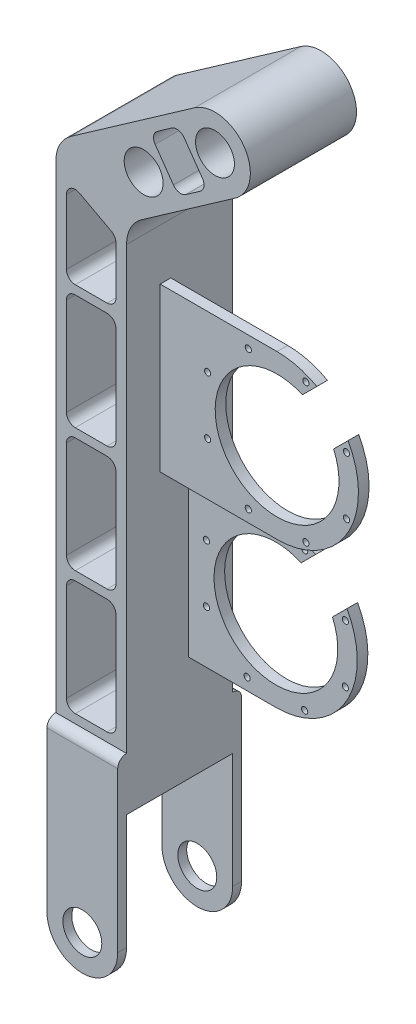
SolidWorks part; units mm, degrees
material "6061 合金"
ref_plane "前视基准面" through (0, 0, 0) normal (0, 0, 1) x (1, 0, 0)
ref_plane "上视基准面" through (0, 0, 0) normal (0, 1, 0) x (1, 0, 0)
ref_plane "右视基准面" through (0, 0, 0) normal (1, 0, 0) x (0, 0, -1)
other "Configuration Table"
sketch "草图1" plane through (0, 0, 0) normal (0, 0, 1) x (1, 0, 0)
  circle A0 centre (0, 0) radius 20
  circle A1 centre (0, 0) radius 11
  dimension "D1" = 40
  dimension "D2" = 22
extrude "凸台-拉伸1" add sketch "草图1" along normal blind 60 contours A1 | A0
ref_plane "基准面1" through (0, 0, 30) normal (0, 0, 1) x (1, 0, 0)
sketch "草图2" plane through (0, 0, 30) normal (0, 0, 1) x (1, 0, 0)
  line L0 (0, 0) -> (-70, -49.0145) construction
  line L1 (-70, -49.0145) -> (-70, -349.0145) construction
  line L2 (0, -57.3148) -> (0, 49.9409) construction
  line L3 (-56.8582, 0) -> (46.4003, 0) construction
  line L4 (-11.4715, 16.383) -> (-90, -38.6032)
  line L5 (11.4715, -16.383) -> (-50, -59.4259)
  line L6 (-90, -38.6032) -> (-90, -349.0145)
  line L7 (-50, -59.4259) -> (-50, -349.0145)
  line L8 (-90, -349.0145) -> (-50, -349.0145)
  circle A2 centre (0, 0) radius 20 construction
  arc A3 (-11.4715, 16.383) -> (11.4715, -16.383) centre (0, 0) ccw
  dimension "D1" = 55
  dimension "D2" = 300
  dimension "D3" = 70
  dimension "D4" = 40
  dimension "D5" = 40
extrude "凸台-拉伸2" add sketch "草图2" along normal mid plane 60 contours L7 L8 L6 L4 A3 L5
sketch "草图4" plane through (0, 0, 60) normal (0, 0, 1) x (1, 0, 0)
  line L0 (-90, -38.6032) -> (-90, -349.0145) construction
  line L1 (-90, -319.0145) -> (-50, -319.0145)
  line L2 (-90, -319.0145) -> (-90, -414.1256)
  line L4 (-50, -319.0145) -> (-50, -414.1256)
  line L5 (-50, -59.4259) -> (-50, -349.0145) construction
  line L6 (-90, -349.0145) -> (-50, -349.0145) construction
  line L7 (0, 0) -> (-70, -414.1256) construction
  arc A0 (-90, -414.1256) -> (-50, -414.1256) centre (-70, -414.1256) ccw
  circle A1 centre (-70, -414.1256) radius 11
  dimension "D3" = 22
  dimension "D1" = 30
  dimension "D2" = 420
extrude "凸台-拉伸3" add sketch "草图4" along normal blind 5
sketch "草图8" plane through (0, 0, 60) normal (0, 0, 1) x (1, 0, 0)
  line L1 (0, 0) -> (-70, -414.1256) construction
  line L2 (0, 0) -> (-40.3295, -29.5556) construction
  line L3 (-40.3295, -29.5556) -> (-70, -414.1256) construction
  circle A0 centre (-40.3295, -29.5556) radius 11
  dimension "D1" = 22
  dimension "D2" = 50
  dimension "D3" = 44.17
extrude "切除-拉伸1" cut sketch "草图8" against normal blind 100
mirror "镜向1" about plane through (0, 0, 30) normal (0, 0, 1) of "凸台-拉伸3"
sketch "草图5" plane through (0, 0, 0) normal (0, 1, 0) x (1, 0, 0)
  line L0 (0, 0) -> (0, -78.0582) construction
ref_plane "基准面2" through (-70, 0, 0) normal (-1, 0, 0) x (0, 0, 1)
sketch "草图7" plane through (-70, 0, 0) normal (-1, 0, 0) x (0, 0, 1)
  line L0 (-34.1239, -414.1256) -> (109.535, -414.1256) construction
fillet "圆角4" radius 20 2 edges at (-90, -38.6032, 30) (-50, -59.4259, 30)
fillet "圆角1" [suppressed] radius 50
fillet "圆角2" [suppressed] radius 3
sketch "草图9" plane through (0, 0, 65) normal (0, 0, 1) x (1, 0, 0)
  circle A0 centre (-70, -414.1256) radius 13
  dimension "D1" = 26
extrude "切除-拉伸2" [suppressed] cut sketch "草图9" against normal blind 0.75
sketch "草图10" plane through (0, 0, -5) normal (0, 0, -1) x (-1, 0, 0)
  circle A0 centre (70, -414.1256) radius 13
  dimension "D1" = 26
extrude "切除-拉伸3" [suppressed] cut sketch "草图10" against normal blind 0.75 contours A0
sketch "草图11" plane through (-90, 0, 0) normal (-1, 0, 0) x (0, 0, 1)
  circle A0 centre (48.5, -118.9949) radius 2.75
  circle A1 centre (48.5, -183.9949) radius 2.75
  circle A2 centre (48.5, -248.9949) radius 2.75
  circle A3 centre (11.5, -248.9949) radius 2.75
  circle A4 centre (11.5, -183.9949) radius 2.75
  circle A5 centre (11.5, -118.9949) radius 2.75
  dimension "D1" = 5.5
extrude "切除-拉伸4" [suppressed] cut sketch "草图11" against normal through all contours A1 | A2 | A0 | A3 | A4 | A5
sketch "草图12" [suppressed] plane through (-90, 0, 0) normal (-1, 0, 0) x (0, 0, 1)
  line L0 (30, -62.0134) -> (30, -339.6946) construction
  line L1 (10, -128.9949) -> (50, -128.9949)
  line L2 (10, -128.9949) -> (10, -173.9949)
  line L3 (10, -173.9949) -> (50, -173.9949)
  line L4 (50, -128.9949) -> (50, -173.9949)
  line L5 (10, -193.9949) -> (50, -193.9949)
  line L6 (10, -193.9949) -> (10, -238.9949)
  line L7 (10, -238.9949) -> (50, -238.9949)
  line L8 (50, -193.9949) -> (50, -238.9949)
  line L9 (10, -258.9949) -> (50, -258.9949)
  line L10 (10, -258.9949) -> (10, -290)
  line L11 (10, -290) -> (50, -290)
  line L12 (50, -258.9949) -> (50, -290)
  line L13 (19.5, -173.9949) -> (40.5, -173.9949)
  line L14 (19.5, -173.9949) -> (19.5, -193.9949)
  line L15 (19.5, -193.9949) -> (40.5, -193.9949)
  line L16 (40.5, -173.9949) -> (40.5, -193.9949)
  line L17 (19.5, -238.9949) -> (40.5, -238.9949)
  line L18 (19.5, -238.9949) -> (19.5, -258.9949)
  line L19 (19.5, -258.9949) -> (40.5, -258.9949)
  line L20 (40.5, -238.9949) -> (40.5, -258.9949)
  line L21 (60, -82.4264) -> (60, -290) construction
  line L22 (0, -290) -> (0, -82.4264) construction
  line L23 (57, -320) -> (3, -320) construction
  circle A0 centre (48.5, -118.9949) radius 2.75 construction
  circle A1 centre (48.5, -183.9949) radius 2.75 construction
  circle A2 centre (48.5, -248.9949) radius 2.75 construction
  dimension "D1" = 10
  dimension "D2" = 10
  dimension "D3" = 10
  dimension "D4" = 8
  dimension "D5" = 10
  dimension "D6" = 10
  dimension "D7" = 10
  dimension "D8" = 30
extrude "减重" [suppressed] cut sketch "草图12" against normal through all contours L0 L1 L2 L3 | L15 L0 L17 L7 L8 L5 | L0 L5 L6 L7 | L19 L0 L11 L12 L9 | L0 L9 L10 L11 | L1 L0 L13 L3 L4
fillet "圆角3" [suppressed] radius 3
sketch "草图13" plane through (0, 0, 60) normal (0, 0, 1) x (1, 0, 0)
  circle A0 centre (0, 0) radius 13
  circle A1 centre (-40.3295, -29.5556) radius 13
  dimension "D1" = 26
  dimension "D2" = 26
extrude "切除-拉伸6" [suppressed] cut sketch "草图13" against normal blind 1.75
sketch "草图14" plane through (0, 0, 0) normal (0, 0, -1) x (-1, 0, 0)
  circle A0 centre (0, 0) radius 13
  circle A1 centre (40.3295, -29.5556) radius 13
  dimension "D1" = 26
  dimension "D2" = 26
extrude "切除-拉伸7" [suppressed] cut sketch "草图14" against normal blind 1.75
sketch "草图15" [suppressed] plane through (0, 0, 0) normal (0, 0, -1) x (-1, 0, 0)
  line L0 (0, 0) -> (70, -350) construction
  line L1 (56.2719, -67.2005) -> (60.1942, -86.8121) construction
  line L2 (70, -350) -> (204.3541, -323.1292) construction
  circle A0 centre (56.2719, -67.2005) radius 2.75
  circle A1 centre (75.2172, -73.6095) radius 2.75
  circle A2 centre (60.1942, -86.8121) radius 2.75
  dimension "D1" = 5.5
  dimension "D2" = 20
  dimension "D3" = 20
  dimension "D4" = 20
  dimension "D5" = 42
  dimension "D6" = 270
extrude "切除-拉伸8" [suppressed] cut sketch "草图15" against normal through all contours A2 | A0 | A1
ref_plane "小腿主干连杆面" through (0, 0, 0) normal (0.986, -0.1667, 0) x (0, 0, -1)
ref_plane "小腿主干对称面" through (0, 0, 30) normal (0, 0, -1) x (-1, 0, 0)
sketch "草图16" plane through (0, 0, 60) normal (0, 0, 1) x (1, 0, 0)
  line L0 (0, 0) -> (-70, -414.1256)
  line L1 (-40.3295, -29.5556) -> (0, 0)
sketch "草图17" plane through (0, 0, 60) normal (0, 0, 1) x (1, 0, 0)
  line L0 (0, 0) -> (-70, -414.1256) construction
  line L1 (117.0967, 32.7533) -> (44.3887, -397.393) construction
  line L2 (85.1281, -156.3752) -> (16.1072, -144.7085)
  line L3 (68.4615, -254.9765) -> (-0.5595, -243.3099)
  circle A0 centre (16.1072, -144.7085) radius 46
  circle A1 centre (-0.5595, -243.3099) radius 46
  dimension "D3" = 92
  dimension "D4" = 92
  dimension "D1" = 110
  dimension "D2" = 70
  dimension "D5" = 180
  dimension "D6" = 280
  dimension "D7" = 40
sketch "草图18" plane through (0, 0, 60) normal (0, 0, 1) x (1, 0, 0)
  line L8 (-50, -69.8372) -> (-50, -319.0145) construction
  line L9 (-50, -98.7085) -> (-50, -190.7085)
  line L11 (-50, -98.7085) -> (16.1072, -98.7085)
  line L20 (-50, -190.7085) -> (16.1072, -190.7085)
  circle A5 centre (16.1072, -144.7085) radius 35
  circle A9 centre (16.1072, -144.7085) radius 46 construction
  arc A10 (16.1072, -190.7085) -> (16.1072, -98.7085) centre (16.1072, -144.7085) ccw
  dimension "D2" = 70
extrude "凸台-拉伸4" add sketch "草图18" against normal blind 6 from offset 19 offset against normal yes
sketch "草图19" plane through (0, 0, 0) normal (0, 0, -1) x (-1, 0, 0)
  line L0 (50, -69.8372) -> (50, -319.0145) construction
  line L1 (50, -197.3099) -> (50, -289.3099)
  line L2 (0.5595, -197.3099) -> (50, -197.3099)
  line L3 (0.5595, -289.3099) -> (50, -289.3099)
  circle A0 centre (0.5595, -243.3099) radius 46 construction
  arc A1 (0.5595, -197.3099) -> (0.5595, -289.3099) centre (0.5595, -243.3099) ccw
  circle A2 centre (0.5595, -243.3099) radius 35
  dimension "D1" = 70
extrude "凸台-拉伸5" add sketch "草图19" against normal blind 6 from offset 19 offset against normal yes
sketch "草图21" plane through (0, 0, 65) normal (0, 0, 1) x (1, 0, 0)
  line L0 (-70, -414.1256) -> (-70, -6.9331) construction
  circle A0 centre (-70, -139.1256) radius 2.6
  circle A1 centre (-70, -314.1256) radius 2.6
  circle A2 centre (-58, -364.1256) radius 2.6
  circle A3 centre (-82, -364.1256) radius 2.6
  dimension "D1" = 5.2
  dimension "D2" = 12
  dimension "D3" = 50
  dimension "D4" = 100
  dimension "D5" = 175
extrude "切除-拉伸9" [suppressed] cut sketch "草图21" against normal through all both and the other way through all
sketch "草图22" plane through (0, 0, 41) normal (0, 0, 1) x (1, 0, 0)
  line L0 (16.1072, -12.4618) -> (16.1072, -144.7085) construction
  line L1 (-0.5595, -243.3099) -> (-0.5595, -131.6862) construction
  circle A0 centre (16.1072, -144.7085) radius 42.5 construction
  circle A1 centre (32.3712, -105.4436) radius 1.75
  circle A2 centre (55.3721, -128.4445) radius 1.75
  circle A3 centre (55.3721, -160.9726) radius 1.75
  circle A4 centre (32.3712, -183.9734) radius 1.75
  circle A5 centre (-0.1568, -183.9734) radius 1.75
  circle A6 centre (-23.1577, -160.9726) radius 1.75
  circle A7 centre (-23.1577, -128.4445) radius 1.75
  circle A8 centre (-0.1568, -105.4436) radius 1.75
  circle A9 centre (-0.5595, -243.3099) radius 42.5 construction
  circle A10 centre (15.7046, -204.045) radius 1.75
  circle A11 centre (38.7054, -227.0458) radius 1.75
  circle A12 centre (38.7054, -259.5739) radius 1.75
  circle A13 centre (15.7046, -282.5747) radius 1.75
  circle A14 centre (-16.8235, -282.5747) radius 1.75
  circle A15 centre (-39.8243, -259.5739) radius 1.75
  circle A16 centre (-39.8243, -227.0458) radius 1.75
  circle A17 centre (-16.8235, -204.045) radius 1.75
  point P22 (16.1072, -144.7085)
  point P43 (-0.5595, -243.3099)
  dimension "D1" = 85
  dimension "D2" = 3.5
  dimension "D4" = 85
  dimension "D5" = 3.5
  dimension "D3" = 8
  dimension "D6" = 8
extrude "切除-拉伸10" cut sketch "草图22" against normal up to surface (22 mm away) up to face at (-35.5595, -243.3099, 19)
sketch "草图23" plane through (0, 0, 60) normal (0, 0, 1) x (1, 0, 0)
  line L0 (-90, -49.0145) -> (-90, -319.0145) construction
  line L1 (-84, -249.0145) -> (-56, -249.0145)
  line L2 (-84, -249.0145) -> (-84, -314.0145)
  line L3 (-84, -314.0145) -> (-56, -314.0145)
  line L4 (-56, -249.0145) -> (-56, -314.0145)
  line L5 (-84, -179.0145) -> (-56, -179.0145)
  line L6 (-84, -179.0145) -> (-84, -244.0145)
  line L7 (-84, -244.0145) -> (-56, -244.0145)
  line L8 (-56, -179.0145) -> (-56, -244.0145)
  line L9 (-84, -109.0145) -> (-56, -109.0145)
  line L10 (-84, -109.0145) -> (-84, -174.0145)
  line L11 (-84, -174.0145) -> (-56, -174.0145)
  line L12 (-56, -109.0145) -> (-56, -174.0145)
  line L13 (-50, -69.8372) -> (-50, -319.0145) construction
  line L14 (-50, -319.0145) -> (-90, -319.0145) construction
  line L19 (-11.4715, 16.383) -> (-81.4715, -32.6315) construction
  line L20 (11.4715, -16.383) -> (-41.4715, -53.4542) construction
  line L21 (-20.3174, 2.8645) -> (-36.7004, -8.607)
  line L22 (-36.7004, -8.607) -> (-20.6403, -31.5433)
  line L23 (-20.6403, -31.5433) -> (-4.2572, -20.0718)
  line L24 (-4.2572, -20.0718) -> (-20.3174, 2.8645)
  line L25 (-84, -54.0145) -> (-84, -104.0145)
  line L26 (-84, -104.0145) -> (-56, -104.0145)
  line L27 (-56, -104.0145) -> (-56, -69.0145)
  line L28 (-56, -69.0145) -> (-84, -54.0145)
  dimension "D1" = 5
  dimension "D2" = 6
  dimension "D3" = 6
  dimension "D4" = 5
  dimension "D5" = 5
  dimension "D6" = 65
  dimension "D7" = 65
  dimension "D8" = 65
  dimension "D9" = 5
  dimension "D10" = 50
  dimension "D11" = 35
  dimension "D14" = 6
  dimension "D15" = 6
  dimension "D16" = 15
  dimension "D17" = 35
extrude "切除-拉伸11" cut sketch "草图23" along direction (0, 0, 1) on the side against the normal up to surface (60 mm away) up to face at (-29.3295, -29.5556, 0)
fillet "圆角6" radius 5 22 edges at (-70, -319.0145, -5) (-70, -319.0145, 65) (-84, -314.0145, 30) (-56, -314.0145, 30) (-56, -249.0145, 30) (-84, -249.0145, 30) (-84, -244.0145, 30) (-56, -244.0145, 30) (-84, -179.0145, 30) (-56, -179.0145, 30) (-84, -174.0145, 30) (-56, -174.0145, 30) (-84, -109.0145, 30) (-56, -109.0145, 30) (-20.3174, 2.8645, 30) (-36.7004, -8.607, 30) (-20.6403, -31.5433, 30) (-4.2572, -20.0718, 30) (-84, -104.0145, 30) (-56, -104.0145, 30) (-56, -69.0145, 30) (-84, -54.0145, 30)
sketch "草图25" plane through (0, 0, 41) normal (0, 0, 1) x (1, 0, 0)
  line L0 (16.1072, -144.7085) -> (96.3528, -64.4629) construction
  line L1 (24.819, -118.3191) -> (42.4966, -135.9968)
  line L2 (42.4966, -135.9968) -> (62.946, -115.5474)
  line L3 (62.946, -115.5474) -> (45.2683, -97.8697)
  line L4 (45.2683, -97.8697) -> (24.819, -118.3191)
  line L5 (-0.5595, -243.3099) -> (81.0037, -161.7467) construction
  line L6 (7.0658, -218.0069) -> (24.7435, -235.6846)
  line L7 (24.7435, -235.6846) -> (48.0489, -212.3792)
  line L8 (48.0489, -212.3792) -> (30.3712, -194.7015)
  line L9 (30.3712, -194.7015) -> (7.0658, -218.0069)
  circle A0 centre (55.3721, -128.4445) radius 1.75 construction
  circle A1 centre (32.3712, -105.4436) radius 1.75 construction
  circle A2 centre (38.7054, -227.0458) radius 1.75 construction
  circle A3 centre (15.7046, -204.045) radius 1.75 construction
  dimension "D1" = 25
  dimension "D2" = 25
  dimension "D3" = 24.8203
  dimension "D4" = 20.4494
  dimension "D5" = 23.2838
  dimension "D6" = 32.9588
extrude "切除-拉伸12" cut sketch "草图25" against normal up to surface (22 mm away) up to face at (13.9546, -204.045, 19)
